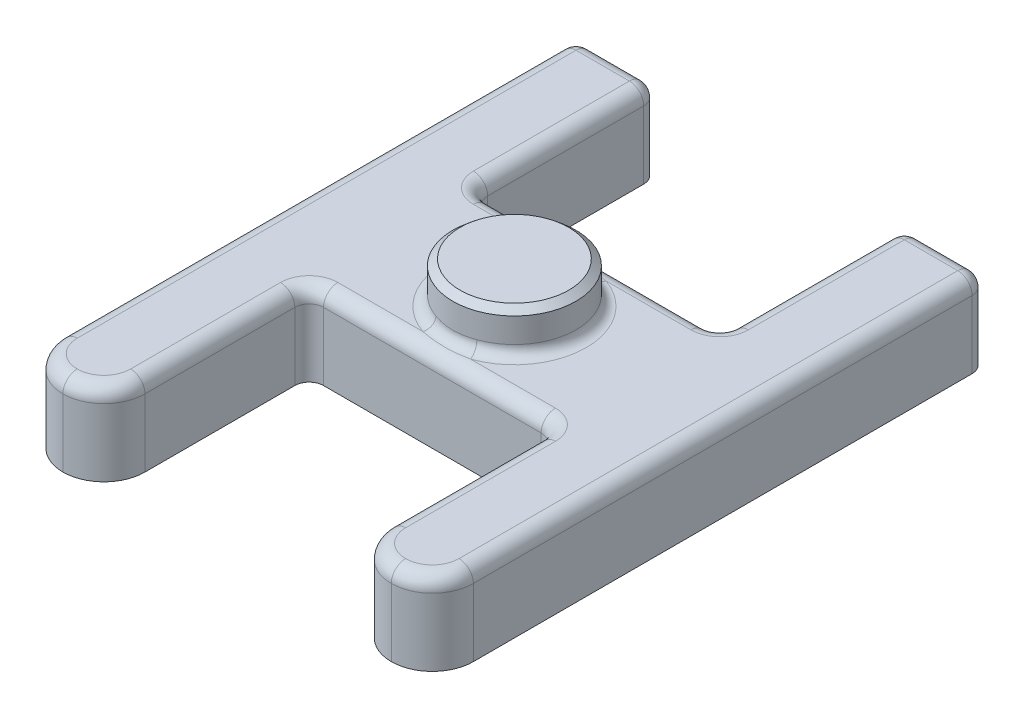
SolidWorks part; units mm, degrees
ref_plane "Front Plane" through (0, 0, 0) normal (0, 0, 1) x (1, 0, 0)
ref_plane "Top Plane" through (0, 0, 0) normal (0, 1, 0) x (1, 0, 0)
ref_plane "Right Plane" through (0, 0, 0) normal (1, 0, 0) x (0, 0, -1)
sketch "Sketch2" plane through (0, 0, 0) normal (0, 0, 1) x (1, 0, 0)
  line L1 (0, 101.6) -> (508, 101.6)
  line L2 (0, 101.6) -> (0, 0)
  line L3 (0, 0) -> (508, 0)
  line L4 (508, 101.6) -> (508, 0)
  dimension "D1" = 101.6
  dimension "D2" = 508
extrude "Boss-Extrude2" add sketch "Sketch2" along normal blind 965.2 contours L2 L1 L4 L3
sketch "Sketch3" plane through (0, 0, 0) normal (0, -1, 0) x (-1, 0, 0)
  line L5 (0, 0) -> (-508, 0) construction
  line L6 (0, -965.2) -> (-508, -965.2) construction
  line L12 (-508, -965.2) -> (-508, 0) construction
  line L13 (0, -965.2) -> (0, 0) construction
  line L17 (-469.9, -228.6) -> (-444.5, -228.6)
  line L18 (-469.9, -228.6) -> (-469.9, -203.2)
  line L19 (-469.9, -203.2) -> (-444.5, -203.2)
  line L20 (-444.5, -228.6) -> (-444.5, -203.2)
  line L21 (-469.9, -228.6) -> (-444.5, -203.2) construction
  line L22 (-469.9, -203.2) -> (-444.5, -228.6) construction
  line L27 (-63.5, -203.2) -> (-38.1, -203.2)
  line L28 (-63.5, -203.2) -> (-63.5, -228.6)
  line L29 (-63.5, -228.6) -> (-38.1, -228.6)
  line L30 (-38.1, -203.2) -> (-38.1, -228.6)
  line L31 (-63.5, -203.2) -> (-38.1, -228.6) construction
  line L32 (-63.5, -228.6) -> (-38.1, -203.2) construction
  circle A0 centre (-50.8, -762) radius 25.4
  circle A1 centre (-457.2, -762) radius 25.4
  point P25 (-469.9, -215.9)
  dimension "D1" = 38.1
  dimension "D2" = 203.2
  dimension "D3" = 203.2
  dimension "D4" = 38.1
  dimension "D5" = 50.8
  dimension "D6" = 50.8
  dimension "D7" = 203.2
  dimension "D8" = 203.2
extrude "Cut-Extrude1" cut sketch "Sketch3" against normal blind 50.8
sketch "Sketch4" plane through (0, 0, 0) normal (0, -1, 0) x (1, 0, 0)
  line L0 (101.6, 965.2) -> (406.4, 965.2)
  line L1 (0, 965.2) -> (508, 965.2) construction
  line L2 (0, 0) -> (508, 0) construction
  line L3 (101.6, 584.2) -> (406.4, 584.2)
  line L4 (0, 965.2) -> (0, 0) construction
  line L5 (508, 965.2) -> (508, 0) construction
  line L6 (406.4, 838.2) -> (406.4, 584.2)
  line L7 (101.6, 381) -> (406.4, 381)
  line L8 (101.6, 0) -> (406.4, 0)
  line L9 (101.6, 838.2) -> (101.6, 584.2)
  line L10 (101.6, 381) -> (101.6, 152.4)
  line L11 (406.4, 381) -> (406.4, 152.4)
  line L12 (0, 838.2) -> (101.6, 838.2)
  line L13 (0, 838.2) -> (0, 965.2)
  line L14 (0, 965.2) -> (101.6, 965.2)
  line L15 (406.4, 838.2) -> (508, 838.2)
  line L16 (508, 838.2) -> (508, 965.2)
  line L17 (508, 965.2) -> (406.4, 965.2)
  line L21 (508, 0) -> (406.4, 0)
  line L22 (101.6, 0) -> (0, 0)
  line L24 (101.6, 152.4) -> (0, 152.4)
  line L25 (0, 152.4) -> (0, 0)
  line L26 (406.4, 152.4) -> (508, 152.4)
  line L27 (508, 152.4) -> (508, 0)
  dimension "D1" = 101.6
  dimension "D2" = 101.6
  dimension "D3" = 127
  dimension "D4" = 228.6
  dimension "D5" = 203.2
  dimension "D6" = 228.6
extrude "Cut-Extrude2" cut sketch "Sketch4" against normal through all both and the other way through all
fillet "Fillet1" radius 17.78 20 edges at (406.4, 50.8, 381) (101.6, 50.8, 381) (406.4, 50.8, 584.2) (101.6, 50.8, 584.2) (508, 101.6, 495.3) (406.4, 101.6, 266.7) (406.4, 101.6, 711.2) (254, 101.6, 584.2) (254, 101.6, 381) (101.6, 101.6, 266.7) (0, 101.6, 495.3) (101.6, 101.6, 711.2) (50.8, 101.6, 838.2) (457.2, 101.6, 838.2) (0, 50.8, 152.4) (50.8, 101.6, 152.4) (101.6, 50.8, 152.4) (406.4, 50.8, 152.4) (457.2, 101.6, 152.4) (508, 50.8, 152.4)
sketch "Sketch5" plane through (0, 101.6, 0) normal (0, 1, 0) x (1, 0, 0)
  circle A0 centre (254, -482.6) radius 76.2
  dimension "D1" = 152.4
fillet "Fillet6" radius 50.8 8 edges at (5.2076, 96.3924, 832.9924) (96.3924, 96.3924, 832.9924) (411.6076, 96.3924, 832.9924) (502.7924, 96.3924, 832.9924) (508, 41.91, 838.2) (406.4, 41.91, 838.2) (101.6, 41.91, 838.2) (0, 41.91, 838.2)
extrude "Boss-Extrude3" add sketch "Sketch5" along normal blind 50.8
fillet "Fillet2" radius 12.7 1 edges at (177.8, 101.6, 482.6)
chamfer "Chamfer1" distance 7.46 angle 50 1 edges at (177.8, 152.4, 482.6) first distance on face at (254, 114.087, 482.6)
